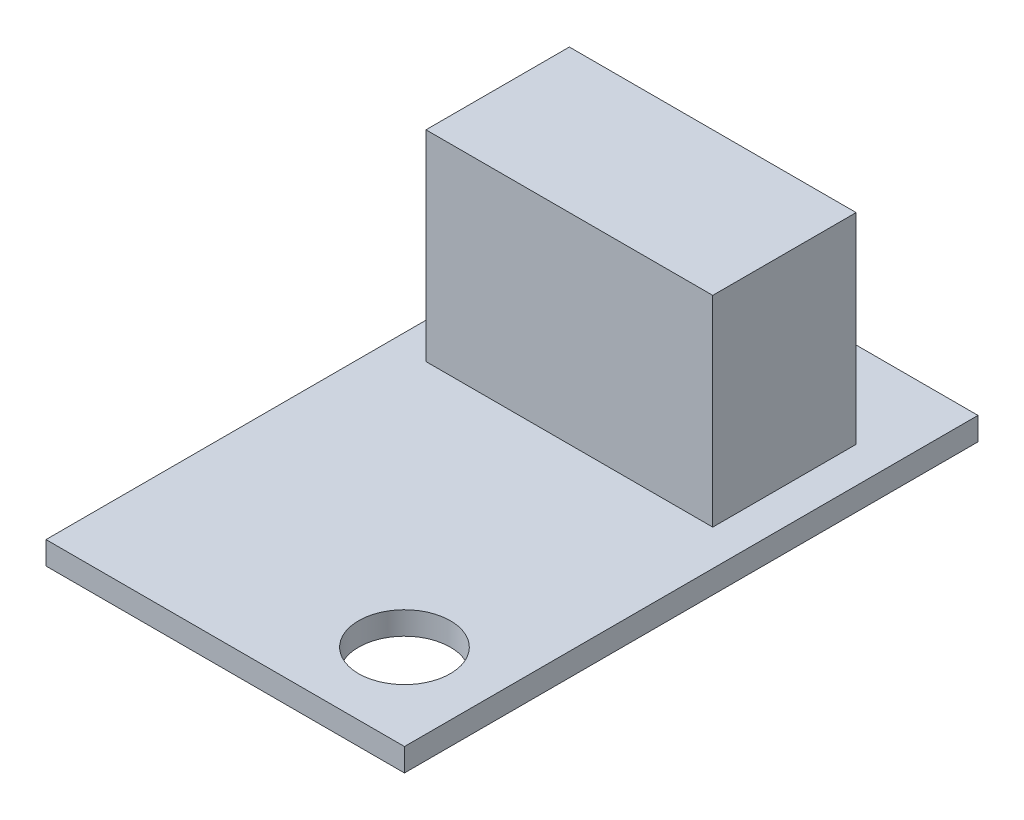
SolidWorks part; units mm, degrees
ref_plane "Front Plane" through (0, 0, 0) normal (0, 0, 1) x (1, 0, 0)
ref_plane "Top Plane" through (0, 0, 0) normal (0, 1, 0) x (1, 0, 0)
ref_plane "Right Plane" through (0, 0, 0) normal (1, 0, 0) x (0, 0, -1)
sketch "Sketch1" plane through (0, 0, 0) normal (0, 1, 0) x (1, 0, 0)
  line L1 (-6.25, 0) -> (6.25, 0)
  line L2 (-6.25, 0) -> (-6.25, 20)
  line L3 (-6.25, 20) -> (6.25, 20)
  line L4 (6.25, 0) -> (6.25, 20)
  circle A0 centre (3.25, 3) radius 1.6
  dimension "D3" = 3.2
  dimension "D1" = 12.5
  dimension "D2" = 20
  dimension "D4" = 3
  dimension "D5" = 3
extrude "Boss-Extrude1" add sketch "Sketch1" along normal blind 0.8
sketch "Sketch2" plane through (0, 0.8, 0) normal (0, 1, 0) x (1, 0, 0)
  line L0 (0, 0) -> (0, 50000) construction
  line L1 (-5, 17) -> (5, 17)
  line L2 (-5, 17) -> (-5, 12)
  line L3 (-5, 12) -> (5, 12)
  line L4 (5, 17) -> (5, 12)
  line L5 (-6.25, 0) -> (6.25, 0) construction
  line L6 (6.25, 20) -> (-6.25, 20) construction
  point P8 (0, 0)
  dimension "D1" = 10
  dimension "D2" = 5
  dimension "D3" = 3
extrude "Boss-Extrude2" add sketch "Sketch2" along normal blind 7
